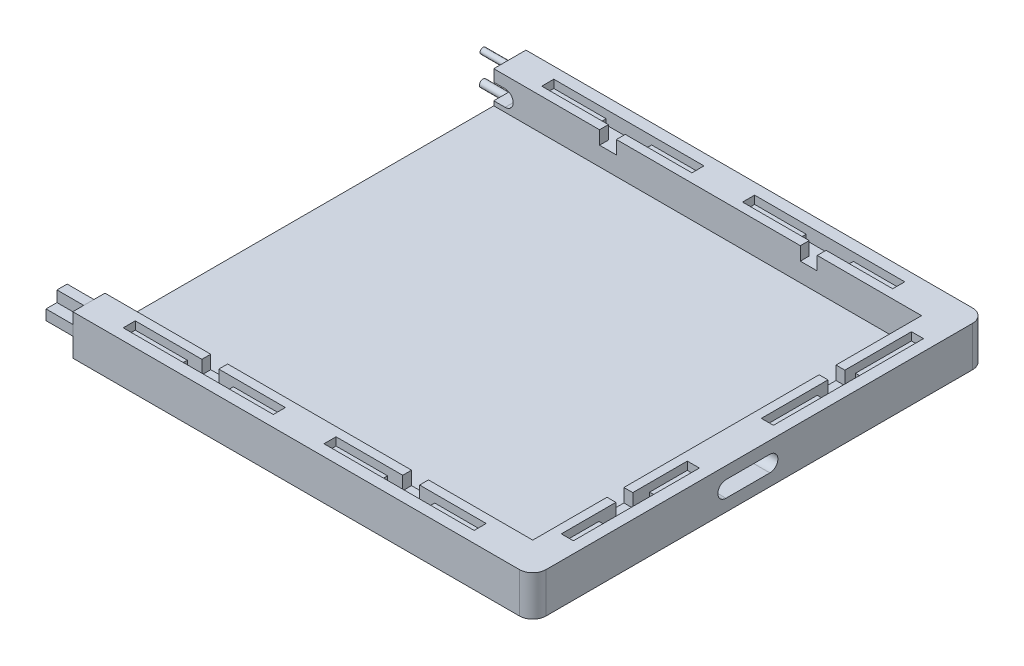
SolidWorks part; units mm, degrees
ref_plane "Front Plane" through (0, 0, 0) normal (0, 0, 1) x (1, 0, 0)
ref_plane "Top Plane" through (0, 0, 0) normal (0, 1, 0) x (1, 0, 0)
ref_plane "Right Plane" through (0, 0, 0) normal (1, 0, 0) x (0, 0, -1)
sketch "Sketch1" plane through (0, 0, 0) normal (0, 1, 0) x (1, 0, 0)
  line L0 (0, 152.7185) -> (0, -149.9342) construction
  line L1 (-90.768, 0) -> (299.0331, 0) construction
  line L2 (0, 72.5) -> (159.54, 72.5)
  line L3 (159.54, 72.5) -> (159.54, -72.5)
  line L4 (159.54, -72.5) -> (0, -72.5)
  line L5 (0, -72.5) -> (0, 72.5)
  dimension "D1" = 159.54
  dimension "D2" = 145
extrude "Boss-Extrude1" add sketch "Sketch1" along normal blind 3
sketch "Sketch3" plane through (0, 0, 0) normal (0, 1, 0) x (1, 0, 0)
  line L0 (0, 105.5814) -> (0, -111.8381) construction
  line L1 (-76.2859, 0) -> (270.0575, 0) construction
  line L2 (0, 72.5) -> (0, 84.5)
  line L3 (0, 84.5) -> (171.54, 84.5)
  line L4 (171.54, 84.5) -> (171.54, -84.5)
  line L5 (171.54, -84.5) -> (0, -84.5)
  line L6 (0, -84.5) -> (0, -72.5)
  line L7 (0, -72.5) -> (159.54, -72.5)
  line L8 (159.54, -72.5) -> (159.54, 72.5)
  line L9 (159.54, 72.5) -> (0, 72.5)
  dimension "D1" = 12
  dimension "D2" = 12
  dimension "D3" = 12
extrude "Boss-Extrude2" add sketch "Sketch3" along normal blind 15
sketch "Sketch4" plane through (0, 15, 0) normal (0, 1, 0) x (1, 0, 0)
  line L0 (45.75, 75.8) -> (45.75, 72.5)
  line L1 (70.6, 75.8) -> (45.75, 75.8)
  line L2 (70.6, 80.3) -> (70.6, 75.8)
  line L3 (14.6, 80.3) -> (70.6, 80.3)
  line L4 (14.6, 75.8) -> (14.6, 80.3)
  line L5 (39.45, 75.8) -> (14.6, 75.8)
  line L6 (39.45, 72.5) -> (39.45, 75.8)
  line L7 (45.75, 72.5) -> (39.45, 72.5)
  line L8 (120.64, 75.8) -> (120.64, 72.5)
  line L9 (145.49, 75.8) -> (120.64, 75.8)
  line L10 (145.49, 80.3) -> (145.49, 75.8)
  line L11 (89.49, 80.3) -> (145.49, 80.3)
  line L12 (89.49, 75.8) -> (89.49, 80.3)
  line L13 (114.34, 75.8) -> (89.49, 75.8)
  line L14 (114.34, 72.5) -> (114.34, 75.8)
  line L15 (120.64, 72.5) -> (114.34, 72.5)
  line L16 (0, 72.5) -> (159.54, 72.5) construction
  line L17 (0, 84.5) -> (0, 72.5) construction
  line L18 (159.54, 72.5) -> (159.54, -72.5) construction
  line L19 (0, 72.5) -> (0, -72.5) construction
  line L20 (145.49, -75.8) -> (120.64, -75.8)
  line L21 (145.49, -80.3) -> (145.49, -75.8)
  line L22 (89.49, -80.3) -> (145.49, -80.3)
  line L23 (89.49, -75.8) -> (89.49, -80.3)
  line L24 (114.34, -75.8) -> (89.49, -75.8)
  line L25 (114.34, -72.5) -> (114.34, -75.8)
  line L26 (120.64, -72.5) -> (114.34, -72.5)
  line L27 (120.64, -75.8) -> (120.64, -72.5)
  line L28 (70.6, -75.8) -> (45.75, -75.8)
  line L29 (70.6, -80.3) -> (70.6, -75.8)
  line L30 (14.6, -80.3) -> (70.6, -80.3)
  line L31 (14.6, -75.8) -> (14.6, -80.3)
  line L32 (39.45, -75.8) -> (14.6, -75.8)
  line L33 (39.45, -72.5) -> (39.45, -75.8)
  line L34 (45.75, -72.5) -> (39.45, -72.5)
  line L35 (45.75, -75.8) -> (45.75, -72.5)
  line L36 (159.54, -72.5) -> (0, -72.5) construction
  line L40 (159.54, -38.5) -> (162.84, -38.5)
  line L49 (159.54, 40.6) -> (162.84, 40.6)
  line L50 (162.84, 40.6) -> (162.84, 65.45)
  line L51 (162.84, 65.45) -> (167.34, 65.45)
  line L52 (167.34, 65.45) -> (167.34, 9.45)
  line L53 (167.34, 9.45) -> (162.84, 9.45)
  line L54 (162.84, 34.3) -> (162.84, 9.45)
  line L55 (159.54, 34.3) -> (162.84, 34.3)
  line L56 (159.54, 40.6) -> (159.54, 34.3)
  line L57 (162.84, -38.5) -> (162.84, -18.15)
  line L58 (162.84, -18.15) -> (167.34, -18.15)
  line L59 (167.34, -18.15) -> (167.34, -65.15)
  line L60 (167.34, -65.15) -> (162.84, -65.15)
  line L61 (162.84, -44.8) -> (162.84, -65.15)
  line L62 (159.54, -44.8) -> (162.84, -44.8)
  line L63 (159.54, -38.5) -> (159.54, -44.8)
  line L64 (0, -72.5) -> (159.54, -72.5) construction
  dimension "D1" = 6.3
  dimension "D2" = 3.3
  dimension "D3" = 4.5
  dimension "D4" = 56
  dimension "D5" = 6.3
  dimension "D6" = 3.3
  dimension "D7" = 4.5
  dimension "D8" = 56
  dimension "D9" = 0
  dimension "D10" = 0
  dimension "D11" = 39.45
  dimension "D12" = 38.9
  dimension "D13" = 56
  dimension "D14" = 39.45
  dimension "D15" = 38.9
  dimension "D16" = 0
  dimension "D17" = 31.9
  dimension "D18" = 6.3
  dimension "D19" = 56
  dimension "D20" = 27.7
  dimension "D21" = 6.3
  dimension "D22" = 47
  dimension "D23" = 56
  dimension "D24" = 3.3
  dimension "D25" = 6.3
  dimension "D26" = 6.3
  dimension "D27" = 3.3
  dimension "D28" = 4.5
  dimension "D29" = 4.5
  dimension "D30" = 3.3
  dimension "D31" = 4.5
  dimension "D32" = 3.3
  dimension "D33" = 4.5
extrude "Cut-Extrude1" cut sketch "Sketch4" against normal blind 3
sketch "Sketch5" plane through (0, 12, 0) normal (0, 1, 0) x (1, 0, 0)
  line L0 (39.45, -75.8) -> (28.5461, -75.8) construction
  line L1 (45.75, -75.8) -> (56.6539, -75.8) construction
  line L2 (39.45, -72.5) -> (39.45, -75.8)
  line L3 (39.45, -75.8) -> (33.9981, -75.8)
  line L4 (33.9981, -75.8) -> (33.9981, -80.3)
  line L5 (33.9981, -80.3) -> (51.2019, -80.3)
  line L6 (51.2019, -80.3) -> (51.2019, -75.8)
  line L7 (45.75, -72.5) -> (39.45, -72.5)
  line L8 (45.75, -72.5) -> (45.75, -75.8)
  line L9 (45.75, -75.8) -> (51.2019, -75.8)
  line L10 (114.34, -75.8) -> (103.0697, -75.8) construction
  line L11 (120.64, -75.8) -> (131.9103, -75.8) construction
  line L12 (114.34, -75.8) -> (108.7049, -75.8)
  line L13 (108.7049, -75.8) -> (108.7049, -80.3)
  line L14 (108.7049, -80.3) -> (126.2751, -80.3)
  line L15 (126.2751, -80.3) -> (126.2751, -75.8)
  line L16 (126.2751, -75.8) -> (120.64, -75.8)
  line L17 (120.64, -75.8) -> (120.64, -72.5)
  line L18 (120.64, -72.5) -> (114.34, -72.5)
  line L19 (114.34, -72.5) -> (114.34, -75.8)
  line L20 (0, -72.5) -> (159.54, -72.5) construction
  line L22 (14.6, -80.3) -> (70.6, -80.3) construction
  line L23 (70.6, -75.8) -> (45.75, -75.8) construction
  line L24 (42.6, -68.4649) -> (42.6, -82.099) construction
  line L26 (89.49, -80.3) -> (145.49, -80.3) construction
  line L27 (114.34, -75.8) -> (89.49, -75.8) construction
  line L28 (117.49, -70.6619) -> (117.49, -81.6393) construction
  line L29 (-14.3619, 0) -> (206.3964, 0) construction
  line L31 (120.64, 72.5) -> (114.34, 72.5)
  line L38 (45.75, 72.5) -> (39.45, 72.5)
  line L48 (159.54, -72.5) -> (159.54, 72.5) construction
  line L49 (159.54, 34.3) -> (162.84, 34.3) construction
  line L56 (162.84, 40.6) -> (159.54, 40.6) construction
  line L59 (157.6179, 36.6875) -> (170.3436, 36.6875) construction
  line L66 (96.0172, 13.3148) -> (96.0172, -25.9889) construction
  line L70 (159.54, -44.8) -> (159.54, -38.5)
  line L75 (159.54, 40.6) -> (162.84, 40.6)
  line L81 (159.54, 34.3) -> (162.84, 34.3)
  line L82 (159.54, 40.6) -> (159.54, 34.3)
  line L94 (158.2993, -40.5875) -> (170.1106, -40.5875) construction
  line L96 (120.64, 72.5) -> (120.64, 75.8)
  line L97 (120.64, 75.8) -> (126.3086, 75.8)
  line L98 (120.64, 75.8) -> (145.49, 75.8) construction
  line L99 (126.3086, 75.8) -> (126.3086, 80.3)
  line L100 (45.75, 72.5) -> (45.75, 75.8)
  line L101 (45.75, 75.8) -> (51.0897, 75.8)
  line L102 (45.75, 75.8) -> (70.6, 75.8) construction
  line L103 (51.0897, 75.8) -> (51.0897, 80.3)
  line L104 (70.6, 80.3) -> (14.6, 80.3) construction
  line L105 (51.0897, 80.3) -> (34.1103, 80.3)
  line L106 (70.6, 80.3) -> (14.6, 80.3) construction
  line L107 (34.1103, 80.3) -> (34.1103, 75.8)
  line L108 (14.6, 75.8) -> (39.45, 75.8) construction
  line L109 (34.1103, 75.8) -> (39.45, 75.8)
  line L110 (39.45, 75.8) -> (39.45, 72.5)
  line L112 (145.49, 80.3) -> (89.49, 80.3) construction
  line L115 (126.3086, 80.3) -> (108.7049, 80.3)
  line L116 (108.7049, 80.3) -> (108.7049, 75.8)
  line L117 (89.49, 75.8) -> (114.34, 75.8) construction
  line L118 (108.7049, 75.8) -> (114.34, 75.8)
  line L119 (114.34, 75.8) -> (114.34, 72.5)
  line L120 (162.84, 40.6) -> (162.84, 44.5797)
  line L121 (162.84, 65.45) -> (162.84, 40.6) construction
  line L122 (162.84, 44.5797) -> (167.34, 44.5797)
  line L123 (167.34, 9.45) -> (167.34, 65.45) construction
  line L124 (167.34, 44.5797) -> (167.34, 30.3203)
  line L125 (167.34, 9.45) -> (167.34, 65.45) construction
  line L126 (167.34, 30.3203) -> (162.84, 30.3203)
  line L127 (162.84, 34.3) -> (162.84, 9.45) construction
  line L128 (162.84, 30.3203) -> (162.84, 34.3)
  line L129 (159.54, -38.5) -> (162.84, -38.5)
  line L130 (162.84, -38.5) -> (162.84, -32.2059)
  line L131 (162.84, -18.15) -> (162.84, -38.5) construction
  line L132 (162.84, -32.2059) -> (167.34, -32.2059)
  line L133 (167.34, -65.15) -> (167.34, -18.15) construction
  line L134 (167.34, -32.2059) -> (167.34, -51.0941)
  line L135 (167.34, -65.15) -> (167.34, -18.15) construction
  line L136 (167.34, -51.0941) -> (162.84, -51.0941)
  line L137 (162.84, -44.8) -> (162.84, -65.15) construction
  line L138 (162.84, -51.0941) -> (162.84, -44.8)
  line L139 (162.84, -44.8) -> (159.54, -44.8)
extrude "Cut-Extrude2" cut sketch "Sketch5" against normal blind 2
sketch "Sketch6" plane through (171.54, 0, 0) normal (1, 0, 0) x (0, 0, -1)
  line L0 (-12.45, 10.5) -> (3.93, 10.5)
  line L1 (-12.45, 4.5) -> (3.93, 4.5)
  line L2 (-15.45, 5.5661) -> (-15.45, 9.4339) construction
  line L5 (-84.5, 7.5) -> (84.5, 7.5) construction
  line L6 (-84.5, 15) -> (-84.5, 0) construction
  line L7 (84.5, 15) -> (84.5, 0) construction
  arc A0 (-12.45, 4.5) -> (-12.45, 10.5) centre (-12.45, 7.5) cw
  arc A1 (3.93, 10.5) -> (3.93, 4.5) centre (3.93, 7.5) cw
  point P6 (-12.45, 10.5)
  point P9 (-15.45, 7.5)
  dimension "D2" = 3
  dimension "D1" = 16.38
  dimension "D3" = 69.05
extrude "Cut-Extrude3" cut sketch "Sketch6" against normal blind 12
sketch "Sketch7" plane through (0, 0, -84.5) normal (0, 0, -1) x (-1, 0, 0)
  line L0 (31.7354, 7.6343) -> (-33.2248, 7.6343) construction
  line L1 (-4.24, 10.6343) -> (12.14, 10.6343)
  line L2 (-4.24, 4.6343) -> (12.14, 4.6343)
  line L3 (-7.24, 4.7002) -> (-7.24, 10.5684) construction
  line L4 (0, 15) -> (0, 0) construction
  line L5 (-171.54, 0) -> (0, 0) construction
  arc A0 (-4.24, 4.6343) -> (-4.24, 10.6343) centre (-4.24, 7.6343) cw
  arc A1 (12.14, 10.6343) -> (12.14, 4.6343) centre (12.14, 7.6343) cw
  point P8 (-4.24, 10.6343)
  point P11 (-7.24, 7.6343)
  dimension "D2" = 3
  dimension "D1" = 16.38
  dimension "D3" = 7.24
  dimension "D4" = 7.6343
extrude "Cut-Extrude4" cut sketch "Sketch7" against normal blind 12
sketch "Sketch8" plane through (0, 0, 0) normal (-1, 0, 0) x (0, 0, 1)
  line L0 (-78.5, 4.6343) -> (-78.5, 0.0234) construction
  line L1 (-72.5, 4.6343) -> (-84.5, 4.6343) construction
  line L2 (-84.5, 12.8171) -> (-72.5, 12.8171) construction
  line L3 (-84.5, 15) -> (-84.5, 10.6343) construction
  line L4 (-72.5, 15) -> (-72.5, 10.6343) construction
  circle A0 centre (-78.5, 12.8171) radius 1.1
  circle A1 centre (-78.5, 2.3288) radius 1.35
  dimension "D1" = 2.2
  dimension "D2" = 2.7
extrude "Boss-Extrude3" add sketch "Sketch8" along normal blind 10
sketch "Sketch9" plane through (0, 0, 0) normal (-1, 0, 0) x (0, 0, 1)
  line L2 (72.5, 9) -> (84.5, 9) construction
  line L3 (72.5, 15) -> (72.5, 3) construction
  line L4 (84.5, 15) -> (84.5, 0) construction
  line L5 (72.5, 3) -> (84.5, 3) construction
  line L6 (78.5, 15) -> (78.5, 3) construction
  line L7 (72.5, 15) -> (84.5, 15) construction
  line L8 (84.4892, 3.011) -> (84.4892, 14.989) construction
  line L9 (84.4892, 14.989) -> (72.5108, 14.989) construction
  line L10 (72.5108, 14.989) -> (72.5117, 3.011) construction
  line L11 (72.5117, 3.011) -> (84.4892, 3.011) construction
  line L12 (84.4892, 3.011) -> (72.5108, 14.989) construction
  line L13 (72.5108, 14.989) -> (84.4892, 14.989) construction
  line L14 (84.4892, 14.989) -> (72.5117, 3.011) construction
  line L15 (78.5, 15.1883) -> (78.5, 3.011) construction
  line L16 (72.5112, 9) -> (83.4994, 9) construction
  line L17 (76.6, 14.989) -> (80.4, 14.989)
  line L18 (84.4892, 7.1) -> (84.4892, 10.9)
  line L19 (80.4, 3.011) -> (76.6, 3.011)
  line L20 (72.5114, 7.1) -> (72.5111, 10.9)
  line L21 (76.6, 14.989) -> (76.6, 10.9)
  line L22 (76.6, 10.9) -> (72.5111, 10.9)
  line L23 (72.5114, 7.1) -> (76.6, 7.1)
  line L24 (76.6, 7.1) -> (76.6, 3.011)
  line L25 (80.4, 3.011) -> (80.4, 7.1)
  line L26 (80.4, 7.1) -> (84.4892, 7.1)
  line L27 (84.4892, 10.9) -> (80.4, 10.9)
  line L28 (80.4, 10.9) -> (80.4, 14.989)
  line L29 (78.5, 9) -> (78.5, 14.989) construction
  line L30 (84.4892, 9) -> (72.5112, 9) construction
  point P26 (78.5, 14.989)
  point P30 (84.4892, 9)
  point P33 (78.5, 3.011)
  point P36 (72.5112, 9)
  point P43 (78.5, 9)
  dimension "D1" = 3.8
  dimension "D2" = 3.8
  dimension "D3" = 3.8
  dimension "D4" = 3.8
  dimension "D5" = 0
extrude "Boss-Extrude5" add sketch "Sketch9" along normal blind 10
fillet "Fillet3" radius 5 1 edges at (171.54, 7.5, 84.5)
fillet "Fillet4" radius 5 1 edges at (171.54, 7.5, -84.5)
